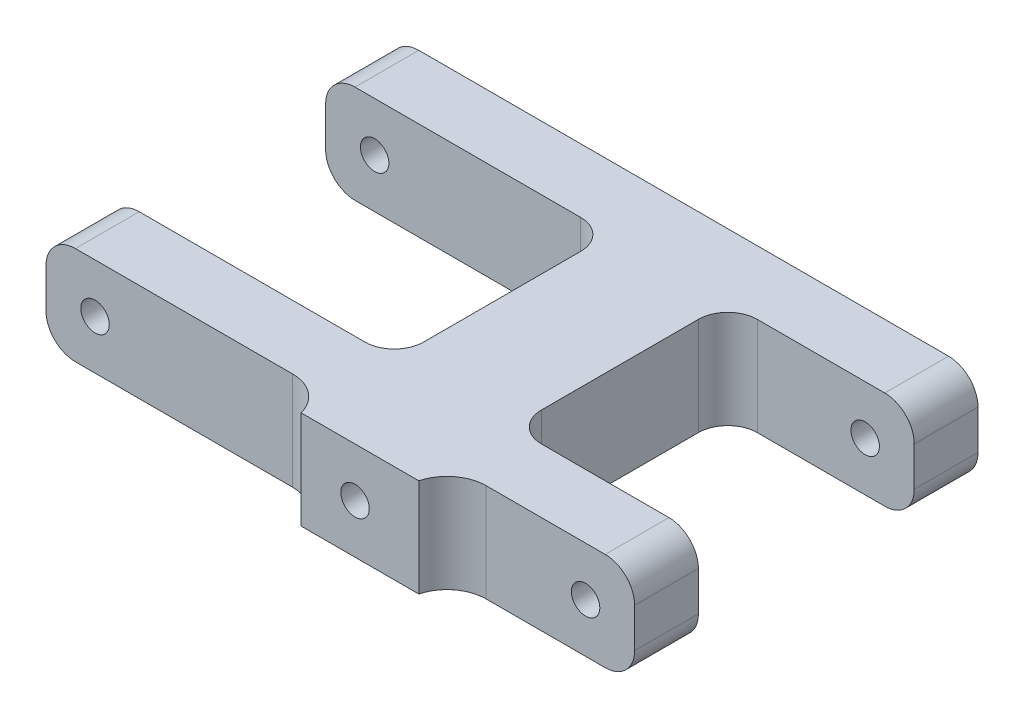
SolidWorks part; units mm, degrees
ref_plane "Front" through (0, 0, 0) normal (0, 0, 1) x (1, 0, 0)
ref_plane "Top" through (0, 0, 0) normal (0, 1, 0) x (1, 0, 0)
ref_plane "Right" through (0, 0, 0) normal (1, 0, 0) x (0, 0, -1)
sketch "Sketch1" plane through (0, 0, 0) normal (0, 1, 0) x (1, 0, 0)
  line L1 (0, 0) -> (60, 0)
  line L2 (0, 0) -> (0, -35)
  line L3 (0, -35) -> (60, -35)
  line L4 (60, 0) -> (60, -35)
  dimension "D1" = 35
  dimension "D2" = 60
extrude "Boss-Extrude1" add sketch "Sketch1" along normal blind 10
sketch "Sketch2" plane through (60, 0, 0) normal (1, 0, 0) x (0, 0, -1)
  line L0 (-35, 10) -> (0, 10) construction
  line L1 (-28.5, 10) -> (-6.5, 10)
  line L2 (-28.5, 10) -> (-28.5, 0)
  line L3 (-28.5, 0) -> (-6.5, 0)
  line L4 (-6.5, 10) -> (-6.5, 0)
  line L5 (-35, 0) -> (0, 0) construction
  line L6 (-35, 10) -> (-35, 0) construction
  line L7 (0, 10) -> (0, 0) construction
  dimension "D1" = 6.5
  dimension "D2" = 6.5
extrude "Cut-Extrude1" cut sketch "Sketch2" against normal blind 19
sketch "Sketch3" plane through (0, 0, 0) normal (-1, 0, 0) x (0, 0, 1)
  line L0 (0, 10) -> (35, 10) construction
  line L1 (6.5, 10) -> (28.5, 10)
  line L2 (6.5, 10) -> (6.5, 0)
  line L3 (6.5, 0) -> (28.5, 0)
  line L4 (28.5, 10) -> (28.5, 0)
  line L5 (0, 0) -> (35, 0) construction
  line L6 (35, 10) -> (35, 0) construction
  line L7 (0, 10) -> (0, 0) construction
  dimension "D1" = 6.5
  dimension "D2" = 6.5
extrude "Cut-Extrude2" cut sketch "Sketch3" against normal blind 29
sketch "Sketch5" plane through (0, 0, 35) normal (0, 0, 1) x (1, 0, 0)
  line L0 (0, 10) -> (60, 10) construction
  line L1 (0, 10) -> (0, 0) construction
  circle A0 centre (5, 5) radius 1.45
  circle A1 centre (55, 5) radius 1.45
  dimension "D1" = 2.9
  dimension "D2" = 5
  dimension "D3" = 5
  dimension "D4" = 2
extrude "Cut-Extrude4" cut sketch "Sketch5" against normal through all
fillet "Fillet1" radius 3 8 edges at (0, 0, 31.75) (0, 10, 31.75) (0, 0, 3.25) (0, 10, 3.25) (60, 10, 3.25) (60, 0, 3.25) (60, 0, 31.75) (60, 10, 31.75)
fillet "Fillet2" radius 3 4 edges at (41, 5, 28.5) (41, 5, 6.5) (29, 5, 28.5) (29, 5, 6.5)
sketch "Sketch7" plane through (0, 0, 35) normal (0, 0, 1) x (1, 0, 0)
  line L0 (3, 10) -> (57, 10) construction
  line L1 (29, 10) -> (41, 10)
  line L2 (29, 10) -> (29, 0)
  line L3 (29, 0) -> (41, 0)
  line L4 (41, 10) -> (41, 0)
  line L5 (3, 0) -> (57, 0) construction
  line L6 (60, 7) -> (60, 3) construction
  line L7 (0, 7) -> (0, 3) construction
  dimension "D1" = 19
  dimension "D2" = 29
extrude "Boss-Extrude2" add sketch "Sketch7" along normal blind 3
sketch "Sketch6" plane through (0, 0, 35) normal (0, 0, 1) x (1, 0, 0)
  line L0 (3, 0) -> (29, 0) construction
  line L2 (0, 7) -> (0, 3) construction
  circle A0 centre (34.5, 5) radius 1.45
  dimension "D1" = 2.9
  dimension "D2" = 5
  dimension "D3" = 34.5
extrude "Cut-Extrude5" cut sketch "Sketch6" against normal blind 15 and the other way blind 3
fillet "Fillet3" radius 4 2 edges at (41, 5, 35) (29, 5, 35)
equation "\"滑动-垂直孔\" = 0.6"
equation "\"滑动-水平孔\"= 0.3"
equation "\"松动-垂直孔\" = 0.3"
equation "\"松动-水平孔\"= 0.1"
equation "\"正常-垂直孔\" = 0.15"
equation "\"正常-水平孔\"= 0"
equation "\"紧缩-垂直孔\"= 0"
equation "\"紧缩-水平孔\"= - 0.1"
equation "\"D1@Sketch5\"=\"紧缩-水平孔\"+3"
equation "\"D1@Sketch6\"=\"紧缩-水平孔\"+3"
